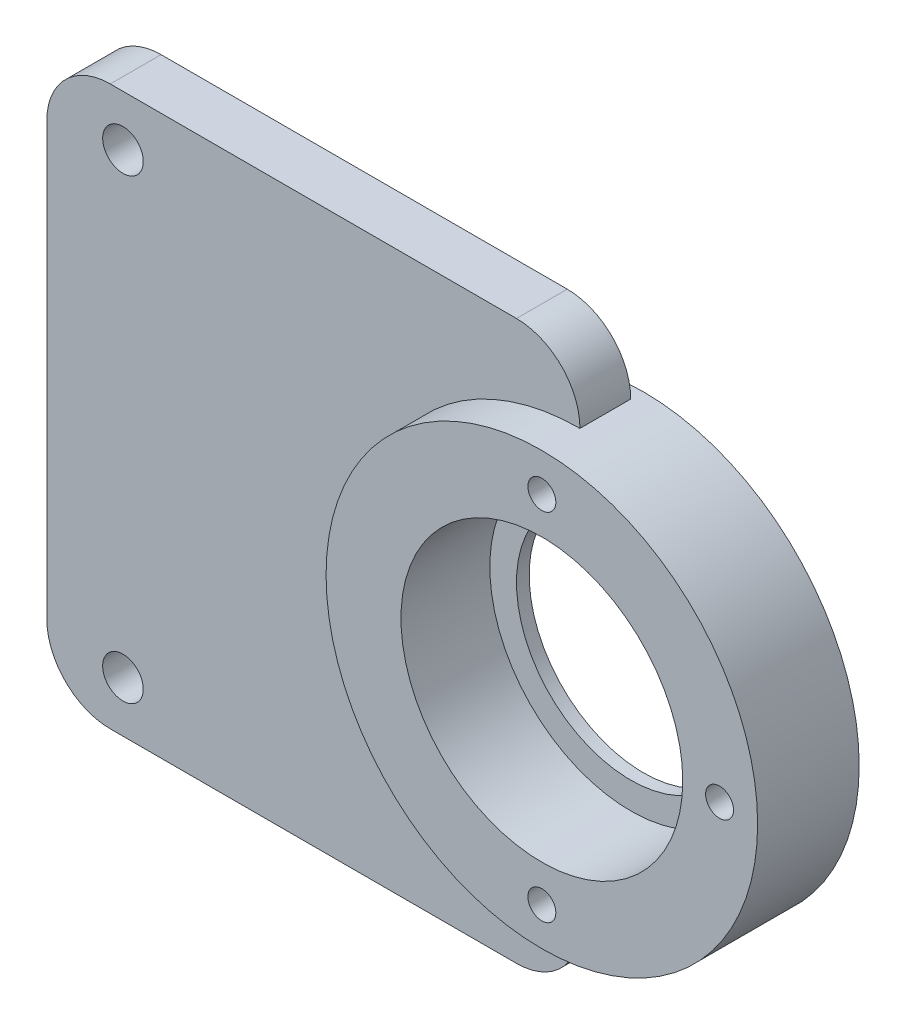
SolidWorks part; units mm, degrees
ref_plane "Front Plane" through (0, 0, 0) normal (0, 0, 1) x (1, 0, 0)
ref_plane "Top Plane" through (0, 0, 0) normal (0, 1, 0) x (1, 0, 0)
ref_plane "Right Plane" through (0, 0, 0) normal (1, 0, 0) x (0, 0, -1)
sketch "Bearing_housing_profile" plane through (0, 0, 0) normal (0, 0, 1) x (1, 0, 0)
  circle A0 centre (0, 0) radius 17
  circle A1 centre (0, 0) radius 11.1
  dimension "D1" = 34
  dimension "D2" = 22.2
extrude "Bearing_housing" add sketch "Bearing_housing_profile" along normal blind 7
sketch "Mounting_web_profile" plane through (0, 0, 0) normal (0, 0, 1) x (1, 0, 0)
  line L1 (-42, -22) -> (0, -22)
  line L2 (-42, -22) -> (-42, 22)
  line L3 (-42, 22) -> (0, 22)
  line L4 (0, -22) -> (0, 22)
  dimension "D1" = 42
  dimension "D2" = 44
  dimension "D3" = 22
extrude "Mounting_web" add sketch "Mounting_web_profile" along normal blind 4
sketch "Bearing_seat_profile" plane through (0, 0, 0) normal (0, 0, 1) x (1, 0, 0)
  circle A0 centre (0, 0) radius 11.1
  dimension "D1" = 22.2
extrude "Bearing_seat" cut sketch "Bearing_seat_profile" along normal through all from offset 50 offset against normal yes
sketch "Inner_outer_race_retaining_lip_profile" plane through (0, 0, 0) normal (0, 0, 1) x (1, 0, 0)
  circle A0 centre (0, 0) radius 17
  circle A1 centre (0, 0) radius 9
  dimension "D1" = 34
  dimension "D2" = 18
extrude "Inner_outer_race_retaining_lip" add sketch "Inner_outer_race_retaining_lip_profile" along normal blind 1 from offset 1 offset against normal yes
sketch "Standoff_fasteners_profile" plane through (0, 0, 0) normal (0, 0, 1) x (1, 0, 0)
  circle A0 centre (-36, -18) radius 1.6
  circle A1 centre (-36, 18) radius 1.6
  dimension "D1" = 3.2
  dimension "D2" = 3.2
  dimension "D3" = 36
  dimension "D4" = 18
  dimension "D5" = 18
extrude "Standoff_fasteners" cut sketch "Standoff_fasteners_profile" along normal through all from offset 50 offset against normal yes
sketch "Bearing_keeper_fasteners_profile" plane through (0, 0, 0) normal (0, 0, 1) x (1, 0, 0)
  circle A0 centre (14, 0) radius 1.1
  circle A1 centre (0, -14) radius 1.1
  circle A2 centre (0, 14) radius 1.1
  dimension "D1" = 2.2
  dimension "D2" = 2.2
  dimension "D3" = 2.2
  dimension "D4" = 14
  dimension "D5" = 14
  dimension "D6" = 14
extrude "Bearing_keeper_fasteners" cut sketch "Bearing_keeper_fasteners_profile" along normal through all from offset 50 offset against normal yes
fillet "Fillet1" radius 5 4 edges at (0, 22, 2) (-42, 22, 2) (-42, -22, 2) (0, -22, 2)
